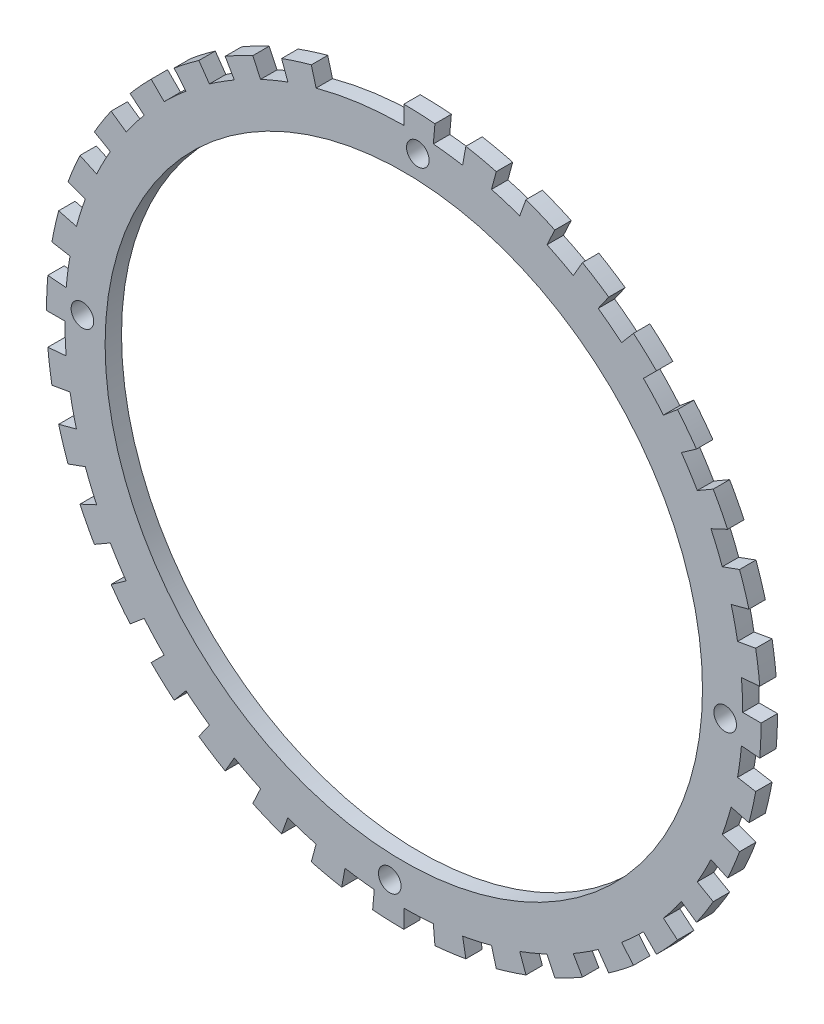
SolidWorks part; units mm, degrees
ref_plane "Front Plane" through (0, 0, 0) normal (0, 0, 1) x (1, 0, 0)
ref_plane "Top Plane" through (0, 0, 0) normal (0, 1, 0) x (1, 0, 0)
ref_plane "Right Plane" through (0, 0, 0) normal (1, 0, 0) x (0, 0, -1)
sketch "Sketch1" plane through (0, 0, 0) normal (0, 0, 1) x (1, 0, 0)
  line L0 (0, 77.75) -> (0, 73.75)
  line L1 (6.7764, 77.4541) -> (6.4277, 73.4694)
  line L2 (0, 73.75) -> (0, 0) construction
  line L3 (6.4277, 73.4694) -> (0, 0) construction
  line L4 (12.8066, 72.6296) -> (13.5011, 76.5688)
  line L5 (12.8066, 72.6296) -> (0, 0) construction
  line L6 (-0.3077, 73.7494) -> (0, 73.75)
  line L7 (20.1232, 75.1007) -> (19.0879, 71.237)
  line L8 (0, 0) -> (3.0534, 69.9334) construction
  line L9 (26.5921, 73.0611) -> (25.224, 69.3023)
  line L10 (32.8586, 70.4654) -> (31.1681, 66.8402)
  line L11 (36.875, 63.8694) -> (38.875, 67.3335)
  line L13 (44.5956, 63.6891) -> (42.3013, 60.4125)
  line L14 (47.4056, 56.4958) -> (49.9767, 59.56)
  line L16 (54.9776, 54.9776) -> (52.1491, 52.1491)
  line L17 (56.4958, 47.4056) -> (59.56, 49.9767)
  line L19 (63.6891, 44.5956) -> (60.4125, 42.3013)
  line L20 (63.8694, 36.875) -> (67.3335, 38.875)
  line L22 (70.4654, 32.8586) -> (66.8402, 31.1681)
  line L23 (69.3023, 25.224) -> (73.0611, 26.5921)
  line L25 (75.1007, 20.1232) -> (71.237, 19.0879)
  line L26 (72.6296, 12.8066) -> (76.5688, 13.5011)
  line L28 (77.4541, 6.7764) -> (73.4694, 6.4277)
  line L29 (73.75, 0) -> (77.75, 0)
  line L31 (77.4541, -6.7764) -> (73.4694, -6.4277)
  line L32 (72.6296, -12.8066) -> (76.5688, -13.5011)
  line L34 (75.1007, -20.1232) -> (71.237, -19.0879)
  line L35 (69.3023, -25.224) -> (73.0611, -26.5921)
  line L37 (70.4654, -32.8586) -> (66.8402, -31.1681)
  line L38 (63.8694, -36.875) -> (67.3335, -38.875)
  line L40 (63.6891, -44.5956) -> (60.4125, -42.3013)
  line L41 (56.4958, -47.4056) -> (59.56, -49.9767)
  line L43 (54.9776, -54.9776) -> (52.1491, -52.1491)
  line L44 (47.4056, -56.4958) -> (49.9767, -59.56)
  line L46 (44.5956, -63.6891) -> (42.3013, -60.4125)
  line L47 (36.875, -63.8694) -> (38.875, -67.3335)
  line L49 (32.8586, -70.4654) -> (31.1681, -66.8402)
  line L50 (25.224, -69.3023) -> (26.5921, -73.0611)
  line L52 (20.1232, -75.1007) -> (19.0879, -71.237)
  line L53 (12.8066, -72.6296) -> (13.5011, -76.5688)
  line L55 (6.7764, -77.4541) -> (6.4277, -73.4694)
  line L56 (0, -73.75) -> (0, -77.75)
  line L58 (-6.7764, -77.4541) -> (-6.4277, -73.4694)
  line L60 (-13.5011, -76.5688) -> (-12.8066, -72.6296)
  line L61 (-20.1232, -75.1007) -> (-19.0879, -71.237)
  line L63 (-26.5921, -73.0611) -> (-25.224, -69.3023)
  line L64 (-32.8586, -70.4654) -> (-31.1681, -66.8402)
  line L66 (-38.875, -67.3335) -> (-36.875, -63.8694)
  line L67 (-44.5956, -63.6891) -> (-42.3013, -60.4125)
  line L69 (-49.9767, -59.56) -> (-47.4056, -56.4958)
  line L70 (-54.9776, -54.9776) -> (-52.1491, -52.1491)
  line L71 (-56.4958, -47.4056) -> (-59.56, -49.9767)
  line L73 (-63.6891, -44.5956) -> (-60.4125, -42.3013)
  line L75 (-67.3335, -38.875) -> (-63.8694, -36.875)
  line L76 (-70.4654, -32.8586) -> (-66.8402, -31.1681)
  line L78 (-73.0611, -26.5921) -> (-69.3023, -25.224)
  line L79 (-75.1007, -20.1232) -> (-71.237, -19.0879)
  line L81 (-76.5688, -13.5011) -> (-72.6296, -12.8066)
  line L82 (-77.4541, -6.7764) -> (-73.4694, -6.4277)
  line L84 (-77.75, 0) -> (-73.75, 0)
  line L85 (-77.4541, 6.7764) -> (-73.4694, 6.4277)
  line L87 (-76.5688, 13.5011) -> (-72.6296, 12.8066)
  line L88 (-75.1007, 20.1232) -> (-71.237, 19.0879)
  line L90 (-73.0611, 26.5921) -> (-69.3023, 25.224)
  line L91 (-70.4654, 32.8586) -> (-66.8402, 31.1681)
  line L93 (-67.3335, 38.875) -> (-63.8694, 36.875)
  line L94 (-63.6891, 44.5956) -> (-60.4125, 42.3013)
  line L96 (-59.56, 49.9767) -> (-56.4958, 47.4056)
  line L97 (-54.9776, 54.9776) -> (-52.1491, 52.1491)
  line L99 (-49.9767, 59.56) -> (-47.4056, 56.4958)
  line L100 (-44.5956, 63.6891) -> (-42.3013, 60.4125)
  line L102 (-38.875, 67.3335) -> (-36.875, 63.8694)
  line L103 (-32.8586, 70.4654) -> (-31.1681, 66.8402)
  line L105 (-26.5921, 73.0611) -> (-25.224, 69.3023)
  line L106 (-20.1232, 75.1007) -> (-19.0879, 71.237)
  line L109 (0, -77.75) -> (0, -73.75) [skipped]
  line L111 (13.5011, 76.5688) -> (12.8066, 72.6296) [skipped]
  line L115 (38.875, 67.3335) -> (36.875, 63.8694) [skipped]
  line L117 (49.9767, 59.56) -> (47.4056, 56.4958) [skipped]
  line L118 (-59.56, -49.9767) -> (-56.4958, -47.4056) [skipped]
  line L119 (59.56, 49.9767) -> (56.4958, 47.4056) [skipped]
  line L121 (67.3335, 38.875) -> (63.8694, 36.875) [skipped]
  line L123 (73.0611, 26.5921) -> (69.3023, 25.224) [skipped]
  line L125 (76.5688, 13.5011) -> (72.6296, 12.8066) [skipped]
  line L127 (77.75, 0) -> (73.75, 0) [skipped]
  line L129 (76.5688, -13.5011) -> (72.6296, -12.8066) [skipped]
  line L131 (73.0611, -26.5921) -> (69.3023, -25.224) [skipped]
  line L133 (67.3335, -38.875) -> (63.8694, -36.875) [skipped]
  line L135 (59.56, -49.9767) -> (56.4958, -47.4056) [skipped]
  line L137 (49.9767, -59.56) -> (47.4056, -56.4958) [skipped]
  line L139 (38.875, -67.3335) -> (36.875, -63.8694) [skipped]
  line L141 (26.5921, -73.0611) -> (25.224, -69.3023) [skipped]
  line L142 (13.5011, -76.5688) -> (12.8066, -72.6296) [skipped]
  circle A0 centre (0, 0) radius 77.75 construction
  circle A1 centre (0, 0) radius 65
  arc A2 (6.4277, 73.4694) -> (12.8066, 72.6296) centre (0, 0) cw
  arc A3 (0, 77.75) -> (6.7764, 77.4541) centre (0, 0) cw
  arc A4 (13.5011, 76.5688) -> (20.1232, 75.1007) centre (0, 0) cw
  arc A5 (19.0879, 71.237) -> (25.224, 69.3023) centre (0, 0) cw
  arc A6 (26.5921, 73.0611) -> (32.8586, 70.4654) centre (0, 0) cw
  arc A7 (31.1681, 66.8402) -> (36.875, 63.8694) centre (0, 0) cw
  arc A8 (38.875, 67.3335) -> (44.5956, 63.6891) centre (0, 0) cw
  arc A9 (42.3013, 60.4125) -> (47.4056, 56.4958) centre (0, 0) cw
  arc A10 (49.9767, 59.56) -> (54.9776, 54.9776) centre (0, 0) cw
  arc A11 (52.1491, 52.1491) -> (56.4958, 47.4056) centre (0, 0) cw
  arc A12 (59.56, 49.9767) -> (63.6891, 44.5956) centre (0, 0) cw
  arc A13 (60.4125, 42.3013) -> (63.8694, 36.875) centre (0, 0) cw
  arc A14 (67.3335, 38.875) -> (70.4654, 32.8586) centre (0, 0) cw
  arc A15 (66.8402, 31.1681) -> (69.3023, 25.224) centre (0, 0) cw
  arc A16 (73.0611, 26.5921) -> (75.1007, 20.1232) centre (0, 0) cw
  arc A17 (71.237, 19.0879) -> (72.6296, 12.8066) centre (0, 0) cw
  arc A18 (76.5688, 13.5011) -> (77.4541, 6.7764) centre (0, 0) cw
  arc A19 (73.4694, 6.4277) -> (73.75, 0) centre (0, 0) cw
  arc A20 (77.75, 0) -> (77.4541, -6.7764) centre (0, 0) cw
  arc A21 (73.4694, -6.4277) -> (72.6296, -12.8066) centre (0, 0) cw
  arc A22 (76.5688, -13.5011) -> (75.1007, -20.1232) centre (0, 0) cw
  arc A23 (71.237, -19.0879) -> (69.3023, -25.224) centre (0, 0) cw
  arc A24 (73.0611, -26.5921) -> (70.4654, -32.8586) centre (0, 0) cw
  arc A25 (66.8402, -31.1681) -> (63.8694, -36.875) centre (0, 0) cw
  arc A26 (67.3335, -38.875) -> (63.6891, -44.5956) centre (0, 0) cw
  arc A27 (60.4125, -42.3013) -> (56.4958, -47.4056) centre (0, 0) cw
  arc A28 (59.56, -49.9767) -> (54.9776, -54.9776) centre (0, 0) cw
  arc A29 (52.1491, -52.1491) -> (47.4056, -56.4958) centre (0, 0) cw
  arc A30 (49.9767, -59.56) -> (44.5956, -63.6891) centre (0, 0) cw
  arc A31 (42.3013, -60.4125) -> (36.875, -63.8694) centre (0, 0) cw
  arc A32 (38.875, -67.3335) -> (32.8586, -70.4654) centre (0, 0) cw
  arc A33 (31.1681, -66.8402) -> (25.224, -69.3023) centre (0, 0) cw
  arc A34 (26.5921, -73.0611) -> (20.1232, -75.1007) centre (0, 0) cw
  arc A35 (19.0879, -71.237) -> (12.8066, -72.6296) centre (0, 0) cw
  arc A36 (13.5011, -76.5688) -> (6.7764, -77.4541) centre (0, 0) cw
  arc A37 (6.4277, -73.4694) -> (0, -73.75) centre (0, 0) cw
  arc A38 (0, -77.75) -> (-6.7764, -77.4541) centre (0, 0) cw
  arc A39 (-6.4277, -73.4694) -> (-12.8066, -72.6296) centre (0, 0) cw
  arc A40 (-13.5011, -76.5688) -> (-20.1232, -75.1007) centre (0, 0) cw
  arc A41 (-19.0879, -71.237) -> (-25.224, -69.3023) centre (0, 0) cw
  arc A42 (-26.5921, -73.0611) -> (-32.8586, -70.4654) centre (0, 0) cw
  arc A43 (-31.1681, -66.8402) -> (-36.875, -63.8694) centre (0, 0) cw
  arc A44 (-38.875, -67.3335) -> (-44.5956, -63.6891) centre (0, 0) cw
  arc A45 (-42.3013, -60.4125) -> (-47.4056, -56.4958) centre (0, 0) cw
  arc A46 (-49.9767, -59.56) -> (-54.9776, -54.9776) centre (0, 0) cw
  arc A47 (-52.1491, -52.1491) -> (-56.4958, -47.4056) centre (0, 0) cw
  arc A48 (-59.56, -49.9767) -> (-63.6891, -44.5956) centre (0, 0) cw
  arc A49 (-60.4125, -42.3013) -> (-63.8694, -36.875) centre (0, 0) cw
  arc A50 (-67.3335, -38.875) -> (-70.4654, -32.8586) centre (0, 0) cw
  arc A51 (-66.8402, -31.1681) -> (-69.3023, -25.224) centre (0, 0) cw
  arc A52 (-73.0611, -26.5921) -> (-75.1007, -20.1232) centre (0, 0) cw
  arc A53 (-71.237, -19.0879) -> (-72.6296, -12.8066) centre (0, 0) cw
  arc A54 (-76.5688, -13.5011) -> (-77.4541, -6.7764) centre (0, 0) cw
  arc A55 (-73.4694, -6.4277) -> (-73.75, 0) centre (0, 0) cw
  arc A56 (-77.75, 0) -> (-77.4541, 6.7764) centre (0, 0) cw
  arc A57 (-73.4694, 6.4277) -> (-72.6296, 12.8066) centre (0, 0) cw
  arc A58 (-76.5688, 13.5011) -> (-75.1007, 20.1232) centre (0, 0) cw
  arc A59 (-71.237, 19.0879) -> (-69.3023, 25.224) centre (0, 0) cw
  arc A60 (-73.0611, 26.5921) -> (-70.4654, 32.8586) centre (0, 0) cw
  arc A61 (-66.8402, 31.1681) -> (-63.8694, 36.875) centre (0, 0) cw
  arc A62 (-67.3335, 38.875) -> (-63.6891, 44.5956) centre (0, 0) cw
  arc A63 (-60.4125, 42.3013) -> (-56.4958, 47.4056) centre (0, 0) cw
  arc A64 (-59.56, 49.9767) -> (-54.9776, 54.9776) centre (0, 0) cw
  arc A65 (-52.1491, 52.1491) -> (-47.4056, 56.4958) centre (0, 0) cw
  arc A66 (-49.9767, 59.56) -> (-44.5956, 63.6891) centre (0, 0) cw
  arc A67 (-42.3013, 60.4125) -> (-36.875, 63.8694) centre (0, 0) cw
  arc A68 (-38.875, 67.3335) -> (-32.8586, 70.4654) centre (0, 0) cw
  arc A69 (-31.1681, 66.8402) -> (-25.224, 69.3023) centre (0, 0) cw
  arc A70 (-26.5921, 73.0611) -> (-20.1232, 75.1007) centre (0, 0) cw
  arc A71 (-19.0879, 71.237) -> (-12.8066, 72.6296) centre (0, 0) cw
  arc A72 (-12.8066, 72.6296) -> (-0.3077, 73.7494) centre (0, 0) cw
  circle A73 centre (3.0534, 69.9334) radius 2.4585
  circle A74 centre (3.0534, 69.9334) radius 2.987 construction
  circle A75 centre (69.9334, -3.0534) radius 2.4585
  circle A76 centre (-3.0534, -69.9334) radius 2.4585
  circle A77 centre (-69.9334, 3.0534) radius 2.4585
  point P12 (3.3914, 69.3023)
  point P34 (0, 0)
  point P252 (0, 0)
  dimension "D1" = 130
  dimension "D2" = 155.5
  dimension "D7" = 4.917
  dimension "D8" = 5.974
  dimension "D3" = 5
  dimension "D4" = 4
  dimension "D6" = 2.5
  dimension "D10" = 70
  dimension "D5" = 35
  dimension "D9" = 4
extrude "Boss-Extrude1" add sketch "Sketch1" along normal blind 3.5719
